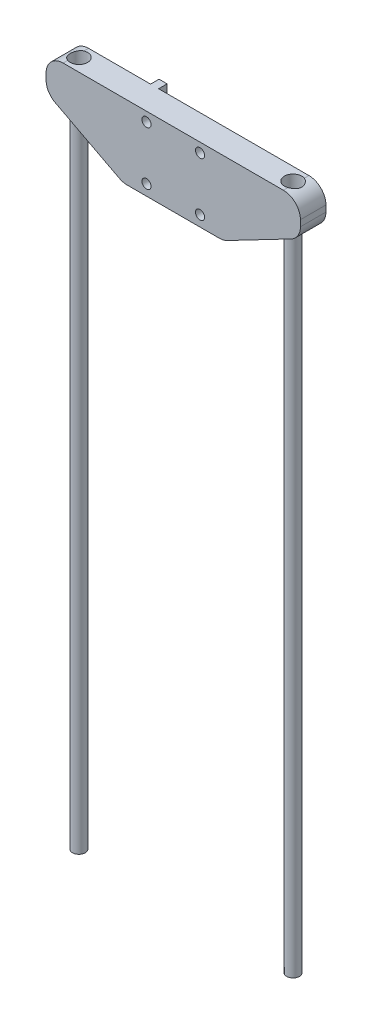
SolidWorks part; units mm, degrees
other "Markup2"
sketch "Sketch8"
other "Markup3"
sketch "Sketch15"
ref_plane "Front Plane" through (0, 0, 0) normal (0, 0, 1) x (1, 0, 0)
ref_plane "Top Plane" through (0, 0, 0) normal (0, 1, 0) x (1, 0, 0)
ref_plane "Right Plane" through (0, 0, 0) normal (1, 0, 0) x (0, 0, -1)
sketch "Sketch2" plane through (0, 0, 0) normal (0, 0, 1) x (1, 0, 0)
  line L0 (-40, 0) -> (-40, -243.6) construction
  line L1 (40, 0) -> (40, -243.6) construction
  line L2 (0, 48.6067) -> (0, -93.2297) construction
  line L3 (-47.5, 12.5) -> (-47.5, 0)
  line L4 (-47.5, 0) -> (-18.75, -15)
  line L5 (-18.75, -15) -> (18.75, -15)
  line L6 (18.75, -15) -> (47.5, 0)
  line L7 (-47.5, 12.5) -> (47.5, 12.5)
  line L8 (47.5, 12.5) -> (47.5, 0)
  line L10 (-42.3812, 0) -> (-37.6188, 0)
  line L11 (-42.3812, 0) -> (-42.3812, -243.6)
  line L12 (-42.3812, -243.6) -> (-37.6187, -243.6)
  line L13 (-37.6188, 0) -> (-37.6187, -243.6)
  line L14 (-10, 9) -> (10, 9) construction
  line L15 (-10, 9) -> (-10, -11) construction
  line L16 (-10, -11) -> (10, -11) construction
  line L17 (10, 9) -> (10, -11) construction
  line L18 (37.6188, -243.6) -> (42.3813, -243.6)
  line L19 (37.6188, -243.6) -> (37.6188, 0)
  line L20 (37.6188, 0) -> (42.3812, 0)
  line L21 (42.3813, -243.6) -> (42.3812, 0)
  dimension "D1" = 80
  dimension "D3" = 4.7625
  dimension "D4" = 20
  dimension "D5" = 20
  dimension "D6" = 228.6
  dimension "12.5" = 12.5
  dimension "D8" = 15
  dimension "D9" = 4
  dimension "D10" = 12.5
  dimension "D11" = 95
  dimension "D12" = 37.5
sketch "Sketch9" plane through (0, 0, 0) normal (0, 1, 0) x (1, 0, 0)
  line L0 (-40, 0) -> (-35, 0) construction
  line L2 (-40, 2.3812) -> (-35, 2.3812)
  line L3 (-40, -2.3812) -> (-35, -2.3812)
  line L4 (0, 20.7896) -> (0, -26.7229) construction
  line L5 (40, 0) -> (35, 0) construction
  line L6 (40, 2.3813) -> (35, 2.3813)
  line L7 (40, -2.3813) -> (35, -2.3813)
  line L8 (-37.5, 2.3812) -> (-37.5, -2.3812) construction
  line L9 (-42.3812, 0) -> (-37.6187, 0) construction
  line L10 (37.5, 2.3813) -> (37.5, -2.3813) construction
  arc A0 (-40, 2.3812) -> (-40, -2.3812) centre (-40, 0) ccw
  arc A1 (-35, -2.3812) -> (-35, 2.3812) centre (-35, 0) ccw
  arc A2 (40, 2.3813) -> (40, -2.3813) centre (40, 0) cw
  arc A3 (35, -2.3813) -> (35, 2.3813) centre (35, 0) cw
  circle A4 centre (-40, 0) radius 1.5
  circle A5 centre (40, 0) radius 1.5
  point P5 (-37.5, 0)
  point P15 (37.5, 0)
  dimension "D1" = 5
  dimension "D3" = 3
  dimension "D2" = 4.7625
sketch "Sketch3" plane through (0, 0, 0) normal (0, 0, 1) x (1, 0, 0)
  line L0 (-47.5, 12.5) -> (-47.5, 0) construction
  line L1 (-47.5, 0) -> (-18.75, -15) construction
  line L2 (-18.75, -15) -> (18.75, -15) construction
  line L3 (18.75, -15) -> (47.5, 0) construction
  line L4 (47.5, 12.5) -> (47.5, 0) construction
  line L5 (-47.5, 12.5) -> (47.5, 12.5) construction
  line L6 (-47.5, 12.5) -> (-47.5, 0)
  line L7 (-47.5, 0) -> (-18.75, -15)
  line L8 (-18.75, -15) -> (18.75, -15)
  line L9 (18.75, -15) -> (47.5, 0)
  line L10 (47.5, 12.5) -> (47.5, 0)
  line L11 (-47.5, 12.5) -> (47.5, 12.5)
extrude "Boss-Extrude1" add sketch "Sketch3" along normal mid plane 9.525
sketch "Sketch10" plane through (0, 0, 0) normal (0, 1, 0) x (1, 0, 0)
  line L0 (40, 2.3813) -> (35, 2.3813) construction
  line L1 (40, -2.3813) -> (35, -2.3813) construction
  line L2 (-40, 2.3812) -> (-35, 2.3812) construction
  line L3 (-40, -2.3812) -> (-35, -2.3812) construction
  line L4 (40, 2.3813) -> (35, 2.3813)
  line L5 (40, -2.3813) -> (35, -2.3813)
  line L6 (-40, 2.3812) -> (-35, 2.3812)
  line L7 (-40, -2.3812) -> (-35, -2.3812)
  arc A0 (35, 2.3813) -> (35, -2.3813) centre (35, 0) ccw construction
  arc A1 (40, -2.3813) -> (40, 2.3813) centre (40, 0) ccw construction
  arc A2 (-35, -2.3812) -> (-35, 2.3812) centre (-35, 0) ccw construction
  arc A3 (-40, 2.3812) -> (-40, -2.3812) centre (-40, 0) ccw construction
  arc A4 (35, 2.3813) -> (35, -2.3813) centre (35, 0) ccw
  arc A5 (40, -2.3813) -> (40, 2.3813) centre (40, 0) ccw
  arc A6 (-35, -2.3812) -> (-35, 2.3812) centre (-35, 0) ccw
  arc A7 (-40, 2.3812) -> (-40, -2.3812) centre (-40, 0) ccw
extrude "Cut-Extrude1" cut sketch "Sketch10" against normal blind 10
sketch "Sketch4" plane through (0, 0, 0) normal (0, 0, 1) x (1, 0, 0)
  line L0 (40, 0) -> (40, -243.6) construction
  line L1 (-40, 0) -> (-40, -243.6) construction
  line L2 (-42.3812, 0) -> (-42.3812, -243.6) construction
  line L3 (-42.3812, -243.6) -> (-37.6187, -243.6) construction
  line L4 (-37.6188, 0) -> (-37.6187, -243.6) construction
  line L5 (-42.3812, 0) -> (-37.6188, 0) construction
  line L6 (40, 0) -> (40, -243.6)
  line L7 (-40, 0) -> (-40, -243.6)
  line L8 (-42.3812, 0) -> (-42.3812, -243.6)
  line L9 (-42.3812, -243.6) -> (-40, -243.6)
  line L10 (-37.6188, 0) -> (-37.6187, -243.6) construction
  line L11 (-42.3812, 0) -> (-40, 0)
  line L12 (-40, -243.6) -> (-40, -275.6996) construction
  line L13 (-40, -243.6) -> (-37.6187, -243.6) construction
  line L14 (-40, 0) -> (-37.6188, 0) construction
  line L15 (40, -243.6) -> (40, -281.3243) construction
  line L16 (37.6188, -243.6) -> (42.3813, -243.6)
  line L17 (37.6188, -243.6) -> (37.6188, 0)
  line L18 (37.6188, 0) -> (42.3812, 0)
  line L19 (42.3813, -243.6) -> (42.3812, 0)
  line L20 (37.6188, -247.4505) -> (40, -247.4505) construction
revolve "Revolve1" add sketch "Sketch4" angle 360 about L12 region at (-41.1906, -121.8, 0)
revolve "Revolve2" add sketch "Sketch4<3>" angle 360 about L15 region at (38.8094, -121.8, 0)
sketch "Sketch4<3>" plane through (0, 0, 0) normal (0, 0, 1) x (1, 0, 0) same geometry as "Sketch4"
hole_wizard "M3 Clearance Hole1" positions "Sketch5" profile "Sketch6" hole size "M3" standard "ANSI Metric" end condition through all
sketch "Sketch5" plane through (0, 0, 4.7625) normal (0, 0, 1) x (1, 0, 0)
  point P0 (-10, 9)
  point P3 (-10, -11)
  point P6 (10, -11)
  point P9 (10, 9)
sketch "Sketch6" plane through (-10, 9, 4.7625) normal (1, 0, 0) x (0, -1, 0)
  line L0 (0, 0) -> (0, 9.525)
  line L1 (0, 9.525) -> (1.7, 9.525)
  line L2 (1.7, 9.525) -> (1.7, 0)
  line L5 (1.7, 0) -> (0, 0)
  line L11 (0, -6.35) -> (0, 107.95) construction
  dimension "Thru Hole Dia." = 3.4
  dimension "Thru Hole Depth" = 9.525
hole_wizard "CBORE for M3 SHCS2" positions "Sketch11" profile "Sketch12" counterbore size "M3" standard "ANSI Metric" end condition through all
sketch "Sketch11" plane through (0, 12.5, 0) normal (0, 1, 0) x (1, 0, 0)
  point P0 (-40, 0)
  point P3 (40, 0)
sketch "Sketch12" plane through (-40, 12.5, 0) normal (1, 0, 0) x (0, 0, 1)
  line L0 (0, 0) -> (0, 256.1)
  line L1 (0, 256.1) -> (1.8, 256.1)
  line L3 (1.8, 256.1) -> (1.8, 9.5)
  line L4 (1.8, 9.5) -> (3.25, 9.5)
  line L5 (3.25, 9.5) -> (3.25, 0)
  line L7 (3.25, 0) -> (0, 0)
  line L11 (0, -6.35) -> (0, 107.95) construction
  dimension "Thru Hole Dia." = 3.6
  dimension "Thru Hole Depth" = 256.1
  dimension "C'Bore Dia." = 6.5
  dimension "C'Bore Depth" = 9.5
hole_wizard "M3x0.5 Tapped Hole1" positions "Sketch13" profile "Sketch14" tap size "M3x0.5" standard "ANSI Metric"
sketch "Sketch13" plane through (0, 0, 0) normal (0, 1, 0) x (1, 0, 0)
  point P0 (-40, 0)
  point P3 (40, 0)
sketch "Sketch14" plane through (-40, 0, 0) normal (1, 0, 0) x (0, 0, 1)
  line L0 (0, 0) -> (0, 8.2511)
  line L1 (0, 8.2511) -> (1.25, 7.5)
  line L2 (1.25, 7.5) -> (1.25, 0)
  line L5 (1.25, 0) -> (0, 0)
  line L10 (0, 8.2511) -> (-1.25, 7.5) construction
  line L11 (0, -6.35) -> (0, 107.95) construction
  dimension "Tap Drill Dia." = 2.5
  dimension "Tap Drill Depth" = 7.5
  dimension "Drill Angle" = 118
fillet "Fillet1" radius 6.35 6 edges at (-18.75, -15, 0) (18.75, -15, 0) (47.5, 0, 0) (47.5, 12.5, 0) (-47.5, 12.5, 0) (-47.5, 0, 0)
sketch "Sketch16" plane through (0, 0, -4.7625) normal (0, 0, -1) x (-1, 0, 0)
  line L0 (-41.15, 12.5) -> (41.15, 12.5) construction
  line L1 (18, -12) -> (15, -12)
  line L2 (18, -12) -> (18, 12.5)
  line L3 (18, 12.5) -> (15, 12.5)
  line L4 (15, -12) -> (15, 12.5)
  line L6 (17.1931, -15) -> (-17.1931, -15) construction
  circle A0 centre (10, -11) radius 1.7 construction
  dimension "D1" = 5
  dimension "D2" = 3
  dimension "D3" = 3
extrude "Boss-Extrude2" add sketch "Sketch16" along normal blind 3.175
